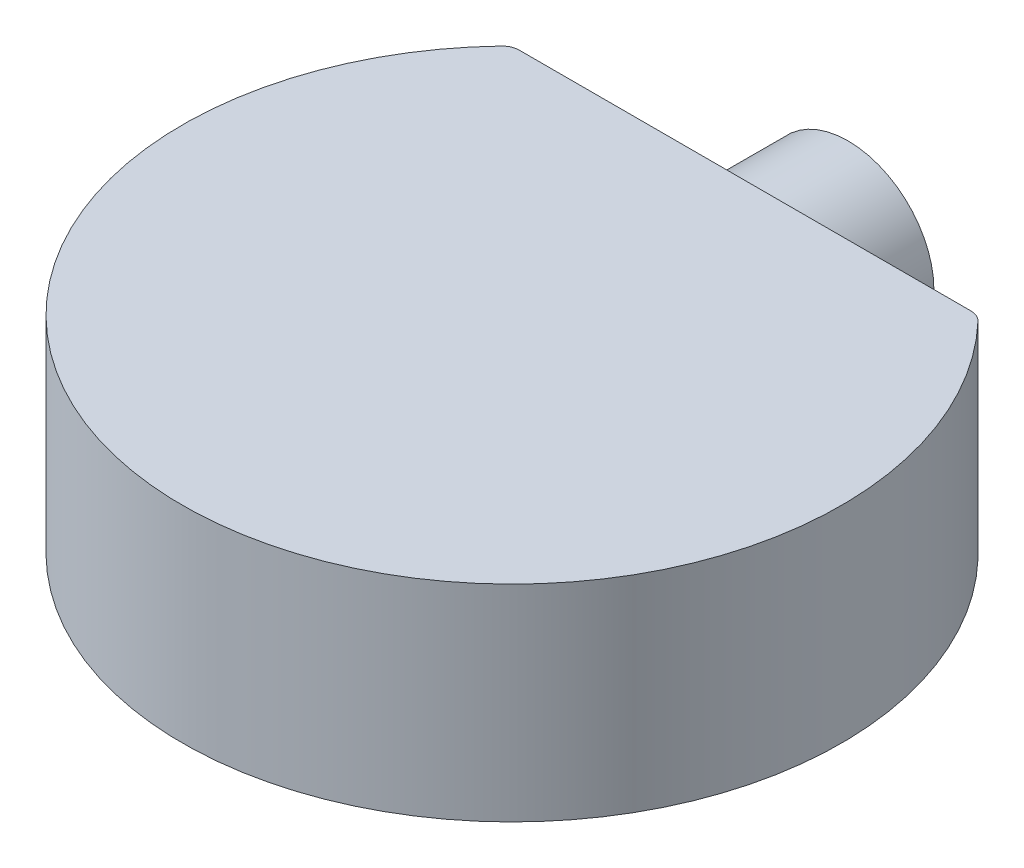
SolidWorks part; units mm, degrees
ref_plane "Front" through (0, 0, 0) normal (0, 0, 1) x (1, 0, 0)
ref_plane "Top" through (0, 0, 0) normal (0, 1, 0) x (1, 0, 0)
ref_plane "Right" through (0, 0, 0) normal (1, 0, 0) x (0, 0, -1)
sketch "Sketch3" plane through (0, 0, 0) normal (0, 1, 0) x (1, 0, 0)
  line L0 (-3.3941, 3.3941) -> (3.3941, 3.3941)
  line L1 (-3.3941, 3.3941) -> (0, 0) construction
  line L2 (0, 0) -> (3.3941, 3.3941) construction
  arc A0 (-3.3941, 3.3941) -> (3.3941, 3.3941) centre (0, 0) ccw
  point P4 (0, 3.3941)
  dimension "D1" = 4.8
extrude "Boss-Extrude4" add sketch "Sketch3" along normal mid plane 3
sketch "Sketch6" plane through (0, 0, -3.3941) normal (0, 0, -1) x (-1, 0, 0)
  circle A0 centre (0, 0) radius 1.25
  circle A1 centre (0, 0) radius 1
  circle A2 centre (0, 0) radius 0.5
  circle A3 centre (0, 0) radius 0.25
  dimension "D1" = 2.5
  dimension "D2" = 2
  dimension "D3" = 1
  dimension "D4" = 0.5
extrude "Boss-Extrude6" add sketch "Sketch6" along normal blind 1.5 contours A2 A3 | A0 A1 region at (1.2146, 0, -3.3941) region at (0.4859, 0, -3.3941)
fillet "Fillet2" radius 0.25 2 edges at (3.3941, 0, -3.3941) (-3.3941, 0, -3.3941)
